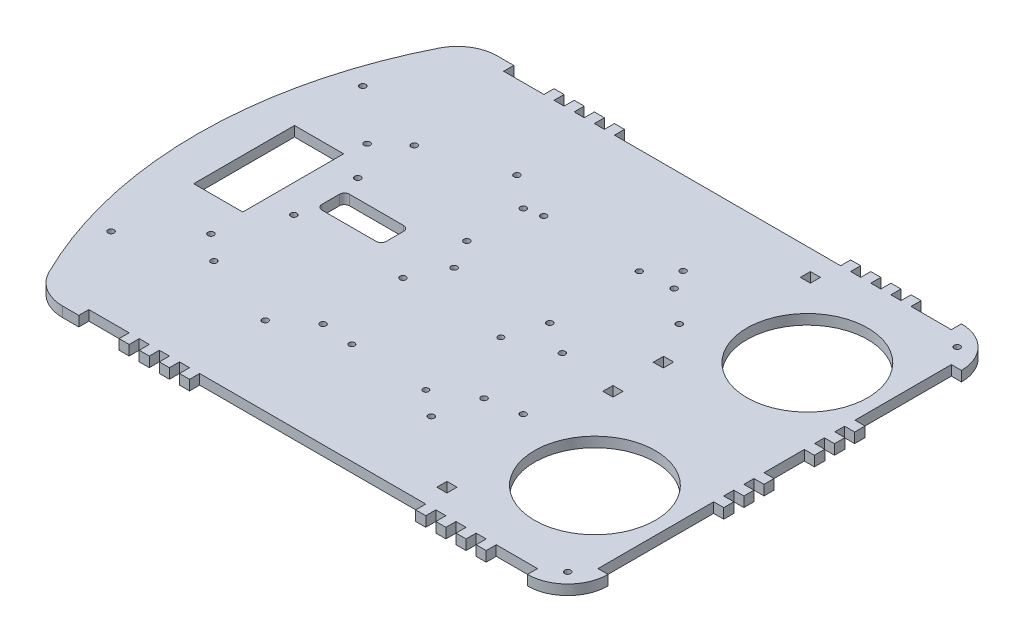
SolidWorks part; units mm, degrees
ref_plane "Front Plane" through (0, 0, 0) normal (0, 0, 1) x (1, 0, 0)
ref_plane "Top Plane" through (0, 0, 0) normal (0, 1, 0) x (1, 0, 0)
ref_plane "Right Plane" through (0, 0, 0) normal (1, 0, 0) x (0, 0, -1)
sketch "main_base_sketch" plane through (0, 0, 0) normal (0, 1, 0) x (1, 0, 0)
  line L1 (111.125, 92.7285) -> (111.125, 23.3533) construction
  line L2 (111.125, -38.1761) -> (111.125, 0) construction
  line L3 (111.125, -99.4864) -> (111.125, -136.4602) construction
  line L4 (111.125, -38.1761) -> (111.125, -99.4864) construction
  line L5 (111.125, 23.3533) -> (111.125, 0) construction
  line L7 (111.125, 92.7285) -> (111.125, 23.3533) construction
  line L9 (111.125, 0) -> (111.125, 23.3533) construction
  line L10 (111.125, 0) -> (111.125, -38.1761) construction
  line L11 (111.125, 0) -> (111.125, -38.1761) construction
  line L20 (-111.125, 0) -> (111.125, 0) construction
  line L22 (111.125, 130.8285) -> (117.475, 130.8285) construction
  line L24 (-94.9614, 130.8285) -> (-94.9614, 124.4785) construction
  line L25 (-94.9614, 124.4785) -> (-69.5614, 124.4785)
  line L26 (187.325, 130.8285) -> (187.325, 124.4785)
  line L27 (-95.6016, -142.8102) -> (111.125, -142.8102) construction
  line L28 (-95.6016, -142.8102) -> (-95.6016, -136.4602)
  line L29 (-95.6016, -136.4602) -> (-70.2016, -136.4602)
  line L30 (187.325, -142.8102) -> (187.325, -136.4602)
  line L32 (-94.9614, 130.8285) -> (-25.1114, 130.8285) construction
  line L33 (111.125, -142.8102) -> (187.325, -142.8102) construction
  line L34 (111.125, -136.4602) -> (111.125, -142.8102) construction
  line L36 (111.125, -136.4602) -> (111.125, -142.8102) construction
  line L37 (-56.8614, 130.8285) -> (-50.5114, 130.8285)
  line L38 (111.125, 12.7) -> (117.4276, 12.7)
  line L39 (-42.259, -8.6817) -> (-76.4089, -8.6817)
  line L40 (-39.084, -5.5067) -> (-39.084, 5.5067)
  line L41 (-42.259, 8.6817) -> (-76.4089, 8.6817)
  line L42 (-79.5839, -5.5067) -> (-79.5839, 5.5067)
  line L43 (-39.084, -8.6817) -> (-79.5839, 8.6817) construction
  line L44 (-39.084, 8.6817) -> (-79.5839, -8.6817) construction
  line L46 (61.595, 63.5) -> (93.345, 63.5) construction
  line L47 (61.595, 63.5) -> (61.595, -63.5) construction
  line L48 (61.595, -63.5) -> (93.345, -63.5) construction
  line L49 (93.345, 63.5) -> (93.345, -63.5) construction
  line L50 (61.595, 63.5) -> (93.345, -63.5) construction
  line L51 (61.595, -63.5) -> (93.345, 63.5) construction
  line L52 (111.125, 12.7) -> (111.125, 19.2555)
  line L53 (111.125, 23.3533) -> (111.125, 0) construction
  line L54 (111.125, 19.2555) -> (117.4276, 19.2555)
  line L55 (-94.9614, 130.8285) -> (-25.1114, 130.8285) construction
  line L58 (111.125, 124.4785) -> (111.125, 92.7285) construction
  line L61 (-95.6016, -142.8102) -> (111.125, -142.8102) construction
  line L62 (111.125, -99.4864) -> (111.125, -136.4602) construction
  line L63 (111.125, 130.8285) -> (117.475, 130.8285) construction
  line L64 (111.125, 124.4785) -> (111.125, 92.7285) construction
  line L65 (111.125, -142.8102) -> (187.325, -142.8102) construction
  line L66 (212.725, 105.4285) -> (212.725, -117.4102) construction
  line L67 (117.4276, 12.7) -> (117.4276, 19.2555)
  line L68 (111.125, -12.7) -> (117.475, -12.7)
  line L69 (111.125, -12.7) -> (111.125, -19.05)
  line L70 (111.125, -19.05) -> (117.475, -19.05)
  line L71 (117.475, -12.7) -> (117.475, -19.05)
  line L72 (111.125, 105.4285) -> (117.475, 105.4285)
  line L73 (111.125, 105.4285) -> (111.125, 111.7785)
  line L74 (111.125, 111.7785) -> (117.475, 111.7785)
  line L75 (117.475, 105.4285) -> (117.475, 111.7785)
  line L76 (111.125, -117.4102) -> (117.475, -117.4102)
  line L77 (111.125, -117.4102) -> (111.125, -123.7602)
  line L78 (111.125, -123.7602) -> (117.475, -123.7602)
  line L79 (117.475, -117.4102) -> (117.475, -123.7602)
  line L80 (212.725, 105.4285) -> (206.375, 105.4285)
  line L81 (212.725, 105.4285) -> (212.725, -117.4102) construction
  line L82 (212.725, -117.4102) -> (206.375, -117.4102)
  line L84 (-69.5614, 130.8285) -> (-63.2114, 130.8285)
  line L85 (-69.5614, 130.8285) -> (-69.5614, 124.4785)
  line L86 (-69.5614, 124.4785) -> (-63.2114, 124.4785) construction
  line L87 (-63.2114, 130.8285) -> (-63.2114, 124.4785)
  line L88 (-56.8614, 130.8285) -> (-56.8614, 124.4785)
  line L89 (-56.8614, 124.4785) -> (-50.5114, 124.4785) construction
  line L90 (-50.5114, 130.8285) -> (-50.5114, 124.4785)
  line L91 (-44.1614, 130.8285) -> (-37.8114, 130.8285)
  line L92 (-44.1614, 130.8285) -> (-44.1614, 124.4785)
  line L93 (-44.1614, 124.4785) -> (-37.8114, 124.4785) construction
  line L94 (-37.8114, 130.8285) -> (-37.8114, 124.4785)
  line L95 (-31.4614, 130.8285) -> (-25.1114, 130.8285)
  line L96 (-31.4614, 130.8285) -> (-31.4614, 124.4785)
  line L97 (-31.4614, 124.4785) -> (-25.1114, 124.4785) construction
  line L98 (-25.1114, 130.8285) -> (-25.1114, 124.4785)
  line L99 (-69.5614, 124.4785) -> (-63.2114, 124.4785) construction
  line L100 (-63.2114, 124.4785) -> (-56.8614, 124.4785)
  line L101 (-56.8614, 124.4785) -> (-50.5114, 124.4785) construction
  line L102 (-50.5114, 124.4785) -> (-44.1614, 124.4785)
  line L103 (-44.1614, 124.4785) -> (-37.8114, 124.4785) construction
  line L104 (-37.8114, 124.4785) -> (-31.4614, 124.4785)
  line L105 (-31.4614, 124.4785) -> (-25.1114, 124.4785) construction
  line L106 (-25.1114, 124.4785) -> (117.475, 124.4785)
  line L107 (149.225, 130.8285) -> (142.875, 130.8285)
  line L108 (161.925, 130.8285) -> (155.575, 130.8285)
  line L109 (161.925, 130.8285) -> (161.925, 124.4785)
  line L110 (161.925, 124.4785) -> (155.575, 124.4785) construction
  line L111 (155.575, 130.8285) -> (155.575, 124.4785)
  line L112 (149.225, 130.8285) -> (149.225, 124.4785)
  line L114 (142.875, 130.8285) -> (142.875, 124.4785)
  line L115 (136.525, 130.8285) -> (130.175, 130.8285)
  line L116 (136.525, 130.8285) -> (136.525, 124.4785)
  line L118 (130.175, 130.8285) -> (130.175, 124.4785)
  line L119 (123.825, 130.8285) -> (117.475, 130.8285) construction
  line L120 (123.825, 130.8285) -> (123.825, 124.4785)
  line L122 (117.475, 130.8285) -> (117.475, 124.4785) construction
  line L123 (117.475, 130.8285) -> (123.825, 130.8285) construction
  line L124 (206.375, 105.4285) -> (206.375, 44.6555)
  line L127 (117.475, 130.8285) -> (117.475, 124.4785) construction
  line L128 (117.475, 130.8285) -> (117.475, 124.4785) construction
  line L129 (145.8534, 124.4785) -> (130.175, 124.4785) [skipped]
  line L130 (149.225, 124.4785) -> (146.7264, 124.4785) [skipped]
  line L131 (123.825, 124.4785) -> (130.175, 124.4785)
  line L132 (136.525, 124.4785) -> (142.875, 124.4785)
  line L133 (149.225, 124.4785) -> (155.575, 124.4785)
  line L134 (161.925, 124.4785) -> (187.325, 124.4785)
  line L135 (133.0367, 124.4785) -> (117.475, 124.4785) [skipped]
  line L136 (123.825, 130.8285) -> (187.325, 130.8285) construction
  line L137 (117.475, 130.8285) -> (123.825, 130.8285) construction
  line L138 (123.825, 130.8285) -> (187.325, 130.8285) construction
  line L139 (-25.1114, 130.8285) -> (111.125, 130.8285) construction
  line L140 (-25.1114, 130.8285) -> (111.125, 130.8285) construction
  line L141 (111.125, 130.8285) -> (111.125, 124.4785) construction
  line L142 (111.125, 130.8285) -> (111.125, 124.4785) construction
  line L143 (123.825, 130.8285) -> (117.475, 130.8285)
  line L144 (117.475, 130.8285) -> (117.475, 124.4785)
  line L151 (206.375, -12.7) -> (212.725, -12.7)
  line L152 (206.375, -12.7) -> (206.375, -19.05) construction
  line L153 (206.375, -19.05) -> (212.725, -19.05)
  line L154 (212.725, -12.7) -> (212.725, -19.05)
  line L155 (206.375, -12.7) -> (206.375, -19.05) construction
  line L156 (206.375, -19.05) -> (206.375, -25.4)
  line L157 (206.375, 19.2555) -> (212.725, 19.2555)
  line L158 (212.725, 19.2555) -> (212.725, 12.7)
  line L159 (212.725, 12.7) -> (206.375, 12.7)
  line L160 (206.375, 24.1792) -> (206.375, 19.2555)
  line L161 (206.375, 12.7) -> (206.375, -12.7)
  line L162 (-70.2016, -136.4602) -> (-70.2016, -142.8102)
  line L163 (-70.2016, -142.8102) -> (-63.8516, -142.8102)
  line L164 (-63.8516, -142.8102) -> (-63.8516, -136.4602)
  line L165 (-70.2016, -136.4602) -> (-63.8516, -136.4602) construction
  line L166 (-63.8516, -136.4602) -> (-57.5016, -136.4602)
  line L167 (-57.5016, -142.8102) -> (-51.1516, -142.8102)
  line L168 (-57.5016, -136.4602) -> (-57.5016, -142.8102)
  line L169 (-51.1516, -142.8102) -> (-51.1516, -136.4602)
  line L170 (-44.8016, -142.8102) -> (-38.4516, -142.8102)
  line L171 (-44.8016, -136.4602) -> (-44.8016, -142.8102)
  line L172 (-38.4516, -142.8102) -> (-38.4516, -136.4602)
  line L173 (-32.1016, -142.8102) -> (-25.7516, -142.8102)
  line L174 (-32.1016, -136.4602) -> (-32.1016, -142.8102)
  line L175 (-25.7516, -142.8102) -> (-25.7516, -136.4602)
  line L176 (-57.5016, -136.4602) -> (-51.1516, -136.4602) construction
  line L177 (-51.1516, -136.4602) -> (-44.8016, -136.4602)
  line L178 (-44.8016, -136.4602) -> (-38.4516, -136.4602) construction
  line L179 (-38.4516, -136.4602) -> (-32.1016, -136.4602)
  line L180 (-32.1016, -136.4602) -> (-25.7516, -136.4602) construction
  line L181 (-25.7516, -136.4602) -> (116.8347, -136.4602)
  line L182 (161.2847, -136.4602) -> (161.2847, -142.8102)
  line L183 (161.2847, -142.8102) -> (154.9347, -142.8102)
  line L184 (154.9347, -142.8102) -> (154.9347, -136.4602)
  line L185 (148.5847, -136.4602) -> (148.5847, -142.8102)
  line L186 (148.5847, -142.8102) -> (142.2347, -142.8102)
  line L187 (142.2347, -142.8102) -> (142.2347, -136.4602)
  line L188 (135.8847, -136.4602) -> (135.8847, -142.8102)
  line L189 (135.8847, -142.8102) -> (129.5347, -142.8102)
  line L190 (129.5347, -142.8102) -> (129.5347, -136.4602)
  line L191 (123.1847, -136.4602) -> (123.1847, -142.8102)
  line L192 (123.1847, -142.8102) -> (116.8347, -142.8102)
  line L193 (116.8347, -142.8102) -> (116.8347, -136.4602)
  line L194 (154.9347, -136.4602) -> (161.2847, -136.4602) construction
  line L195 (161.2847, -136.4602) -> (187.325, -136.4602)
  line L196 (142.2347, -136.4602) -> (148.5847, -136.4602) construction
  line L197 (148.5847, -136.4602) -> (154.9347, -136.4602)
  line L198 (129.5347, -136.4602) -> (135.8847, -136.4602) construction
  line L199 (135.8847, -136.4602) -> (142.2347, -136.4602)
  line L200 (116.8347, -136.4602) -> (123.1847, -136.4602) construction
  line L201 (123.1847, -136.4602) -> (129.5347, -136.4602)
  line L202 (212.725, 25.4) -> (206.375, 25.4)
  line L203 (212.725, 31.9555) -> (212.725, 25.4)
  line L204 (206.375, 31.9555) -> (212.725, 31.9555)
  line L205 (212.725, 38.1) -> (206.375, 38.1)
  line L206 (212.725, 44.6555) -> (212.725, 38.1)
  line L207 (206.375, 44.6555) -> (212.725, 44.6555)
  line L208 (206.375, 31.9555) -> (206.375, 25.4) construction
  line L209 (206.375, 25.4) -> (206.375, 24.1792)
  line L210 (206.375, 44.6555) -> (206.375, 38.1) construction
  line L211 (206.375, 38.1) -> (206.375, 31.9555)
  line L212 (206.375, -31.75) -> (212.725, -31.75)
  line L213 (212.725, -25.4) -> (212.725, -31.75)
  line L214 (206.375, -25.4) -> (212.725, -25.4)
  line L215 (206.375, -44.45) -> (212.725, -44.45)
  line L216 (212.725, -38.1) -> (212.725, -44.45)
  line L217 (206.375, -38.1) -> (212.725, -38.1)
  line L218 (206.375, -25.4) -> (206.375, -31.75) construction
  line L219 (206.375, -31.75) -> (206.375, -38.1)
  line L220 (206.375, -38.1) -> (206.375, -44.45) construction
  line L221 (206.375, -44.45) -> (206.375, -117.4102)
  line L225 (-95.5505, 130.8285) -> (-157.7358, 130.8285) construction
  line L229 (-131.2964, 28.9076) -> (-100.3373, 28.9076)
  line L230 (-131.2964, 28.9076) -> (-131.2964, -34.6891)
  line L231 (-131.2964, -34.6891) -> (-100.3373, -34.6891)
  line L238 (-100.3373, 28.9076) -> (-100.3373, -34.6891)
  line L248 (-94.9614, 130.8285) -> (-95.5505, 130.8285) construction
  line L254 (-94.9614, 130.8285) -> (-95.5505, 130.8285) construction
  line L257 (-94.9614, 130.8285) -> (-105.2412, 130.8285)
  line L258 (-95.5505, 130.8285) -> (-94.9614, 130.8285) construction
  line L259 (-95.6016, -142.8102) -> (-105.7982, -142.8102)
  line L260 (-94.9614, 124.4785) -> (-94.9614, 130.8285)
  line L261 (-94.9614, 130.8285) -> (-95.5505, 130.8285) construction
  line L267 (-97.1554, -142.8102) -> (-95.6016, -142.8102) construction
  line L294 (-94.9614, 130.8285) -> (-95.5505, 130.8285) construction
  line L295 (-157.7358, 130.8285) -> (-157.7358, -142.8102) construction
  line L296 (-157.7358, -142.8102) -> (-97.1554, -142.8102) construction
  line L297 (-95.5505, 130.8285) -> (-157.7358, 130.8285) construction
  circle A0 centre (-82.6643, 55.7457) radius 1.905
  circle A1 centre (-13.8303, 55.7457) radius 1.905
  arc A2 (-76.4089, -8.6817) -> (-79.5839, -5.5067) centre (-76.4089, -5.5067) cw
  arc A3 (-42.259, -8.6817) -> (-39.084, -5.5067) centre (-42.259, -5.5067) ccw
  arc A4 (-39.084, 5.5067) -> (-42.259, 8.6817) centre (-42.259, 5.5067) ccw
  arc A5 (-76.4089, 8.6817) -> (-79.5839, 5.5067) centre (-76.4089, 5.5067) ccw
  circle A10 centre (-3.2843, 57.9936) radius 1.905
  circle A11 centre (-13.8303, 20.1549) radius 1.905
  circle A12 centre (-3.2843, 1.5294) radius 1.905
  circle A13 centre (-82.6643, 20.1549) radius 1.905
  circle A14 centre (-82.6643, -20.1549) radius 1.905
  circle A15 centre (-13.8303, -20.1549) radius 1.905
  circle A16 centre (-82.6643, -70.5685) radius 1.905
  circle A17 centre (-13.8303, -70.5685) radius 1.905
  circle A18 centre (6.29, -72.5476) radius 1.796
  circle A19 centre (54.55, -74.1351) radius 1.796
  circle A20 centre (49.47, -21.7476) radius 1.796
  circle A21 centre (57.0407, 1.5294) radius 1.905
  circle A22 centre (57.0407, 57.9936) radius 1.905
  circle A23 centre (-98.425, 41.8224) radius 1.905
  circle A24 centre (-34.0871, 71.9636) radius 1.905
  circle A25 centre (70.6863, 71.9636) radius 1.905
  circle A26 centre (98.425, 41.8224) radius 1.905
  circle A27 centre (98.425, -56.6452) radius 1.905
  circle A28 centre (70.6863, -86.7864) radius 1.905
  circle A29 centre (-34.0871, -86.7864) radius 1.905
  circle A30 centre (-98.425, -56.6452) radius 1.905
  circle A31 centre (77.47, -60.325) radius 1.905
  circle A32 centre (77.47, 59.5313) radius 1.905
  circle A33 centre (77.47, -10.9537) radius 1.905
  arc A34 (212.725, -117.4102) -> (187.325, -142.8102) centre (187.325, -117.4102) cw
  arc A35 (212.725, 105.4285) -> (187.325, 130.8285) centre (187.325, 105.4285) ccw
  circle A37 centre (160.02, 60.9785) radius 38.1
  circle A38 centre (160.02, -72.9602) radius 38.1
  arc A41 (-127.9188, 116.8691) -> (-128.5327, -128.7374) centre (116.7138, -6.5464) ccw
  arc A42 (-127.9188, 116.8691) -> (-105.2412, 130.8285) centre (-105.2412, 105.4285) cw
  arc A43 (-128.5327, -128.7374) -> (-105.7982, -142.8102) centre (-105.7982, -117.4102) ccw
  circle A44 centre (-131.2964, 71.9636) radius 1.905
  circle A45 centre (-131.2964, -86.7864) radius 1.905
  circle A46 centre (198.6177, 116.8691) radius 1.905
  circle A47 centre (198.6177, -128.7374) radius 1.905
  point P16 (-120.3614, 130.8285)
  point P19 (212.725, -142.8102)
  point P40 (-59.334, 0)
  point P46 (-121.0016, -142.8102)
  point P111 (77.47, -63.5)
  point P113 (77.47, 0)
  point P123 (0, 0)
  dimension "D1" = 3.175
  dimension "D44" = 3.81
  dimension "D45" = 3.81
  dimension "D46" = 3.81
  dimension "D47" = 3.592
  dimension "D48" = 3.592
  dimension "D49" = 3.592
  dimension "D7" = 63.5
  dimension "D12" = 25.4
  dimension "D13" = 25.4
  dimension "D21" = 63.5
  dimension "D24" = 76.2
  dimension "D26" = 76.2
  dimension "D14" = 25.4
  dimension "D30" = 3.81
  dimension "D8" = 4
  dimension "D9" = 40.4999
  dimension "D10" = 17.3633
  dimension "D11" = 4
  dimension "D15" = 104.7734
  dimension "D16" = 74.077
  dimension "D17" = 104.835
  dimension "D18" = 12.7
  dimension "D19" = 6.35
  dimension "D20" = 6.35
  dimension "D22" = 40.4387
  dimension "D23" = 54.0843
  dimension "D25" = 60.325
  dimension "D27" = 10.2799
  dimension "D28" = 10.1966
  dimension "D29" = 6.5555
  dimension "D32" = 6.35
  dimension "D33" = 6.35
  dimension "D34" = 68.834
  dimension "D35" = 48.26
  dimension "D37" = 20.1549
  dimension "D38" = 20.1549
  dimension "D39" = 56.4642
  dimension "D40" = 35.7997
  dimension "D41" = 54.0843
  dimension "D42" = 61.655
  dimension "D43" = 23.277
  dimension "D50" = 1.5875
  dimension "D51" = 127
  dimension "D52" = 31.75
  dimension "D53" = 17.78
  dimension "D54" = 3.175
  dimension "D55" = 3.9688
  dimension "D56" = 70.485
  dimension "D57" = 38.1
  dimension "D59" = 101.6
  dimension "D60" = 6.3026
  dimension "D61" = 12.7
  dimension "D62" = 12.7
  dimension "D63" = 6.35
  dimension "D64" = 6.35
  dimension "D65" = 6.35
  dimension "D66" = 6.35
  dimension "D67" = 12.7
  dimension "D68" = 12.7
  dimension "D69" = 6.35
  dimension "D70" = 6.35
  dimension "D71" = 4
  dimension "D73" = 6.35
  dimension "D76" = 3
  dimension "D77" = 3
  dimension "D75" = 4
extrude "main_base" add sketch "main_base_sketch" along normal blind 6.35
